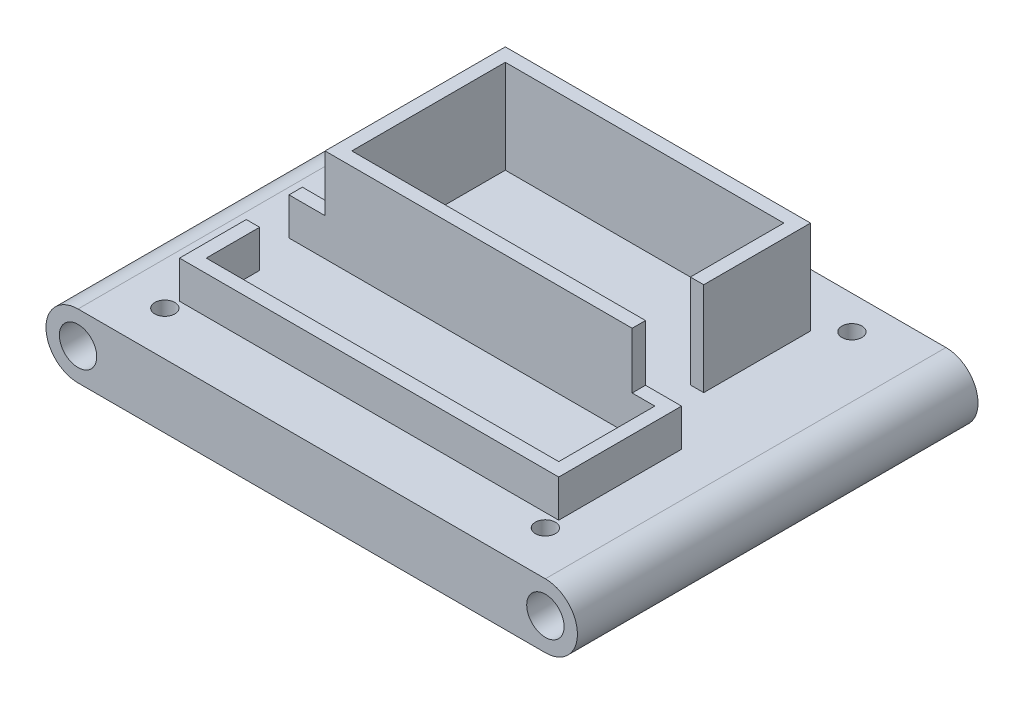
SolidWorks part; units mm, degrees
ref_plane "Front Plane" through (0, 0, 0) normal (0, 0, 1) x (1, 0, 0)
ref_plane "Top Plane" through (0, 0, 0) normal (0, 1, 0) x (1, 0, 0)
ref_plane "Right Plane" through (0, 0, 0) normal (1, 0, 0) x (0, 0, -1)
sketch "Sketch1" plane through (0, 0, 0) normal (0, 0, 1) x (1, 0, 0)
  line L0 (0, -55) -> (0, 55) construction
  line L1 (-44.45, 6.096) -> (44.45, 6.096)
  line L2 (-44.45, -6.096) -> (44.45, -6.096)
  arc A0 (44.45, -6.096) -> (44.45, 6.096) centre (44.45, 0) ccw
  arc A1 (-44.45, -6.096) -> (-44.45, 6.096) centre (-44.45, 0) cw
  circle A2 centre (-44.45, 0) radius 3.556
  circle A3 centre (44.45, 0) radius 3.556
extrude "Boss-Extrude1" add sketch "Sketch1" along normal blind 76.2
sketch "Sketch2" plane through (0, -6.096, 0) normal (0, -1, 0) x (1, 0, 0)
  circle A0 centre (-9.144, 69.215) radius 1.905
  circle A1 centre (27.051, 60.833) radius 1.905
  circle A2 centre (-28.956, 69.215) radius 1.905
  circle A3 centre (-28.956, 6.985) radius 1.905
  circle A4 centre (-9.144, 6.985) radius 1.905
  circle A5 centre (11.049, 60.833) radius 1.905
  circle A6 centre (11.049, 15.367) radius 1.905
  circle A7 centre (27.051, 15.367) radius 1.905
  dimension "D1" = 2
  dimension "D2" = 2
  dimension "D3" = 2
  dimension "D4" = 2
extrude "Cut-Extrude1" cut sketch "Sketch2" against normal blind 6.604
sketch "Sketch3" plane through (0, 6.096, 0) normal (0, 1, 0) x (1, 0, 0)
  line L1 (-29.21, -12.7) -> (28.8477, -12.7)
  line L2 (-29.21, -12.7) -> (-29.21, -10.16)
  line L3 (-29.21, -10.16) -> (28.8477, -10.16)
  line L4 (28.8477, -12.7) -> (28.8477, -10.16)
  line L5 (-29.21, -44.45) -> (29.21, -44.45)
  line L6 (-29.21, -44.45) -> (-29.21, -41.91)
  line L7 (-29.21, -41.91) -> (29.21, -41.91)
  line L8 (29.21, -44.45) -> (29.21, -41.91)
  line L9 (-29.21, -41.91) -> (-26.67, -41.91)
  line L10 (-29.21, -41.91) -> (-29.21, -15.24)
  line L11 (-29.21, -15.24) -> (-26.67, -15.24)
  line L12 (-26.67, -41.91) -> (-26.67, -15.24)
  line L17 (28.8477, -15.24) -> (26.3077, -15.24)
  line L18 (28.8477, -15.24) -> (28.8477, -30.48)
  line L19 (28.8477, -30.48) -> (26.3077, -30.48)
  line L20 (26.3077, -15.24) -> (26.3077, -30.48)
  line L21 (-29.21, -12.7) -> (-26.67, -12.7)
  line L22 (-29.21, -12.7) -> (-29.21, -15.24)
  line L23 (-29.21, -15.24) -> (-26.67, -15.24)
  line L24 (-26.67, -12.7) -> (-26.67, -15.24)
  line L25 (28.8477, -12.7) -> (26.3077, -12.7)
  line L26 (28.8477, -12.7) -> (28.8477, -15.24)
  line L27 (28.8477, -15.24) -> (26.3077, -15.24)
  line L28 (26.3077, -12.7) -> (26.3077, -15.24)
  point P0 (0, 0)
  point P1 (0, 0)
  dimension "D1" = 2.54
  dimension "D2" = 2.54
  dimension "D3" = 58.42
  dimension "D4" = 2.54
  dimension "D5" = 2.54
  dimension "D6" = 15.24
extrude "Boss-Extrude2" add sketch "Sketch3" along normal blind 17.78 contours L1 L4 L3 L2 | L7 L12 L1 L10 | L5 L8 L7 L6 | L24 L1 L22 L11 | L1 L28 L17 L26 | L18 L19 L20 L17 region at (-0.1811, 6.096, 11.43) region at (-27.94, 6.096, 13.97) region at (-27.94, 6.096, 28.575) region at (27.5777, 6.096, 13.97) region at (0, 6.096, 43.18)
sketch "Sketch4" plane through (0, 6.096, 0) normal (0, 1, 0) x (1, 0, 0)
  line L1 (29.21, -44.45) -> (36.068, -44.45)
  line L2 (29.21, -44.45) -> (29.21, -41.91)
  line L3 (29.21, -41.91) -> (36.068, -41.91)
  line L4 (36.068, -44.45) -> (36.068, -41.91)
  line L5 (-29.21, -44.45) -> (-36.068, -44.45)
  line L6 (-29.21, -44.45) -> (-29.21, -41.91)
  line L7 (-29.21, -41.91) -> (-36.068, -41.91)
  line L8 (-36.068, -44.45) -> (-36.068, -41.91)
  line L13 (36.068, -44.45) -> (33.528, -44.45)
  line L14 (36.068, -44.45) -> (36.068, -62.738)
  line L15 (36.068, -62.738) -> (33.528, -62.738)
  line L16 (33.528, -44.45) -> (33.528, -62.738)
  line L17 (-36.068, -62.738) -> (36.068, -62.738)
  line L18 (-36.068, -62.738) -> (-36.068, -65.278)
  line L19 (-36.068, -65.278) -> (36.068, -65.278)
  line L20 (36.068, -62.738) -> (36.068, -65.278)
  line L21 (-36.068, -62.738) -> (-33.528, -62.738)
  line L22 (-36.068, -62.738) -> (-36.068, -52.578)
  line L23 (-36.068, -52.578) -> (-33.528, -52.578)
  line L24 (-33.528, -62.738) -> (-33.528, -52.578)
  line M19 (-29.21, -44.45) -> (-29.21, -10.16)
  line M27 (29.21, -41.91) -> (29.21, -44.45)
  dimension "D1" = 6.858
  dimension "D2" = 6.858
  dimension "D3" = 10.16
  dimension "D5" = 18.288
  dimension "D6" = 2.54
  dimension "D7" = 2.54
extrude "Boss-Extrude3" add sketch "Sketch4" along normal blind 7.112 contours L8 L5 L7 M19 | L17 L24 L23 L22 | L20 L15 L17 L18 L19 | L1 L16 L15 L14 | L1 L4 L3 M27 region at (32.639, 6.096, 43.18) region at (34.798, 6.096, 53.594) region at (0, 6.096, 64.008) region at (-34.798, 6.096, 57.658) region at (-32.639, 6.096, 43.18)
sketch "Sketch5" plane through (0, 6.096, 0) normal (0, 1, 0) x (1, 0, 0)
  circle A2 centre (36.068, -67.818) radius 1.905
  circle A3 centre (32.9117, -6.35) radius 1.905
extrude "Cut-Extrude3" cut sketch "Sketch5" against normal blind 7.112 contours A2 | A3 region at (36.068, 6.096, 67.818) region at (32.9117, 6.096, 6.35)
sketch "Sketch6" plane through (0, 6.096, 0) normal (0, 1, 0) x (1, 0, 0)
  circle A0 centre (-36.322, -67.818) radius 1.905
  circle A1 centre (-33.274, -6.35) radius 1.905
extrude "Cut-Extrude4" cut sketch "Sketch6" against normal blind 7.112 contours A1 | A0 region at (-36.322, 6.096, 67.818) region at (-33.274, 6.096, 6.35)
